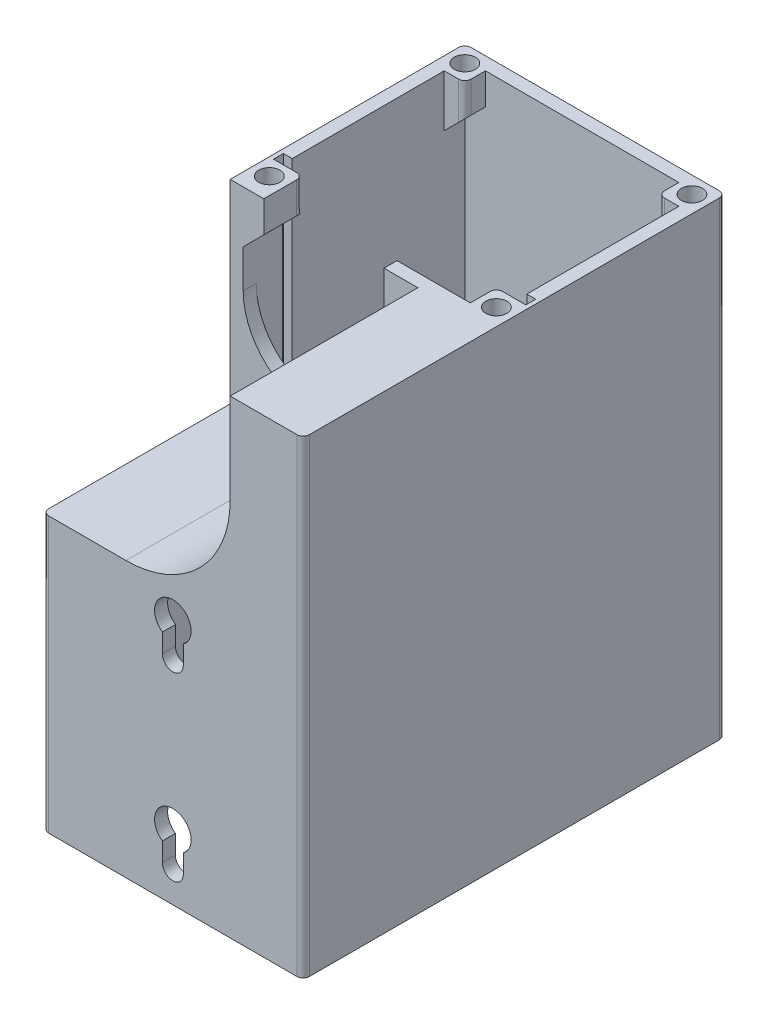
SolidWorks part; units mm, degrees
ref_plane "前基準面" through (0, 0, 0) normal (0, 0, 1) x (1, 0, 0)
ref_plane "上基準面" through (0, 0, 0) normal (0, 1, 0) x (1, 0, 0)
ref_plane "右基準面" through (0, 0, 0) normal (1, 0, 0) x (0, 0, -1)
sketch "草圖1" plane through (0, 0, 0) normal (0, 1, 0) x (1, 0, 0)
  line L1 (-25, -22.5) -> (25, -22.5)
  line L2 (-25, -22.5) -> (-25, 22.5)
  line L3 (-25, 22.5) -> (25, 22.5)
  line L4 (25, -22.5) -> (25, 22.5)
  line L5 (-25, -22.5) -> (25, 22.5) construction
  line L6 (-25, 22.5) -> (25, -22.5) construction
  line L7 (-22.5, -20) -> (22.5, -20)
  line L8 (-22.5, -20) -> (-22.5, 20)
  line L9 (-22.5, 20) -> (22.5, 20)
  line L10 (22.5, -20) -> (22.5, 20)
  line L11 (-22.5, -20) -> (22.5, 20) construction
  line L12 (-22.5, 20) -> (22.5, -20) construction
  point P0 (0, 0)
  point P6 (0, 0)
  point P11 (0, 0)
  point P12 (0, 0)
  dimension "D1" = 50
  dimension "D2" = 2.5
  dimension "D3" = 2.5
  dimension "D4" = 40
extrude "填料-伸長1" add sketch "草圖1" against normal blind 90
sketch "草圖2" plane through (0, 0, 0) normal (0, 1, 0) x (1, 0, 0)
  line L1 (24.2, -15) -> (-24.2, -15)
  line L2 (24.2, -15) -> (24.2, -13.1)
  line L3 (24.2, -13.1) -> (-24.2, -13.1)
  line L4 (-24.2, -15) -> (-24.2, -13.1)
  line L6 (-25, 22.5) -> (-25, -22.5) construction
  line L7 (25, -22.5) -> (25, 22.5) construction
  line L8 (-22.5, -20) -> (22.5, -20) construction
  dimension "D1" = 1.9
  dimension "D2" = 0.8
  dimension "D3" = 0.8
  dimension "D4" = 5
extrude "除料-伸長1" cut sketch "草圖2" against normal blind 36
sketch "草圖3" plane through (0, 0, 22.5) normal (0, 0, 1) x (1, 0, 0)
  line L0 (-25, -90) -> (-25, 0) construction
  line L1 (-25, 0) -> (25, 0) construction
  line L2 (-22.5, -17.3) -> (-22.5, 0)
  line L3 (-22.5, 0) -> (4.5, 0)
  line L4 (4.5, 0) -> (4.5, -17.3)
  circle A0 centre (-9, -17.3) radius 13.5
  line M3 (25, 0) -> (-25, 0)
  dimension "D3" = 27
  dimension "D1" = 16
  dimension "D2" = 17.3
extrude "除料-伸長2" cut sketch "草圖3" against normal up to surface (2.5 mm away) contours A0 L4 L2 M3 | A0 region at (-22.1793, -8.65, 22.5) region at (-9, -17.3, 22.5) up to face at (0, -45, 20)
sketch "草圖4" plane through (0, 0, 22.5) normal (0, 0, 1) x (1, 0, 0)
  line L0 (11, 0) -> (11, -17.3)
  line L1 (4.5, 0) -> (25, 0) construction
  line L2 (-9, -37.3) -> (-25, -37.3)
  line L3 (-25, -90) -> (-25, 0) construction
  line L4 (-25, -37.3) -> (-25, -90)
  line L5 (-25, -90) -> (25, -90)
  line L6 (25, -90) -> (25, 0)
  line L7 (25, 0) -> (11, 0)
  arc A0 (11, -17.3) -> (-9, -37.3) centre (-9, -17.3) cw
  arc A1 (-22.5, -17.3) -> (4.5, -17.3) centre (-9, -17.3) ccw construction
  arc A2 (-22.5, -17.3) -> (4.5, -17.3) centre (-9, -17.3) ccw construction
  circle A3 centre (-9, -17.3) radius 15 construction
  point P20 (-13.6326, -36.7561)
  point P21 (0, 0)
  point P22 (0, 0)
  point P23 (10.5076, -21.7106)
  dimension "D1" = 30
  dimension "D2" = 5
extrude "填料-伸長2" add sketch "草圖4" along normal blind 36
sketch "草圖5" plane through (-25, -90, 58.5) normal (0, -1, 0) x (1, 0, 0)
  line L0 (47.5, -38.5) -> (47.5, -78.5) construction
  line L1 (2.5, -38.5) -> (47.5, -38.5)
  line L2 (2.5, -38.5) -> (2.5, -2.5)
  line L3 (2.5, -2.5) -> (47.5, -2.5)
  line L4 (47.5, -38.5) -> (47.5, -2.5)
  line L7 (0, 0) -> (50, 0) construction
  dimension "D1" = 2.5
extrude "除料-伸長3" cut sketch "草圖5" against normal offset from surface (50.2 mm away) 2.5 up to face at (-17, -37.3, 40.5)
sketch "草圖6" plane through (0, 0, 20) normal (0, 0, -1) x (-1, 0, 0)
  line L0 (-22.5, -2.5) -> (-22.5, -39.8)
  line L1 (-22.5, -39.8) -> (22.5, -39.8) construction
  line L2 (-22.5, -39.8) -> (9, -39.8)
  line L3 (-22.5, -2.5) -> (-13.5, -2.5)
  line L4 (-13.5, -2.5) -> (-13.5, -17.3)
  line L5 (-25, 0) -> (25, 0) construction
  line L7 (-22.5, -90) -> (-22.5, 0) construction
  arc A0 (-13.5, -17.3) -> (9, -39.8) centre (9, -17.3) ccw
  arc A1 (-11, -17.3) -> (9, -37.3) centre (9, -17.3) ccw construction
  dimension "D1" = 2.5
  dimension "D2" = 2.5
extrude "除料-伸長4" cut sketch "草圖6" against normal up to surface (36 mm away) up to face at (0, -64.9, 56)
ref_plane "平面2" through (0, -38.5, 0) normal (0, 1, 0) x (1, 0, 0)
sketch "草圖7" plane through (0, -38.5, 0) normal (0, 1, 0) x (1, 0, 0)
  line L1 (-20.3, -13.1) -> (-22.5, -13.1)
  line L2 (-20.3, -13.1) -> (-20.3, -15)
  line L3 (-20.3, -15) -> (-22.5, -15)
  line L4 (-22.5, -13.1) -> (-22.5, -15)
  line L5 (24.2, -13.1) -> (22.5, -13.1) construction
  line L6 (22.5, -15) -> (24.2, -15) construction
  line L7 (-22.5, 20) -> (-22.5, -56) construction
  dimension "D1" = 2.2
extrude "填料-伸長3" add sketch "草圖7" against normal blind 30
chamfer "導角1" distance 2.2 angle 45 2 edges at (-20.3, -38.5, 14.05) (-20.3, -68.5, 14.05)
sketch "草圖8" plane through (0, -90, 0) normal (0, -1, 0) x (1, 0, 0)
  line L0 (-25, 58.5) -> (25, 58.5) construction
  line L1 (-25, -22.5) -> (-25, 58.5) construction
  line L2 (25, -22.5) -> (-25, -22.5) construction
  line L3 (-22.5, 56) -> (-18.55, 56)
  line L4 (-22.5, 56) -> (-22.5, 52.05)
  line L5 (-22.5, 52.05) -> (-18.55, 52.05)
  line L6 (-18.55, 56) -> (-18.55, 52.05)
  line L7 (22.5, 56) -> (18.55, 56)
  line L8 (22.5, 56) -> (22.5, 52.05)
  line L9 (22.5, 52.05) -> (18.55, 52.05)
  line L10 (18.55, 56) -> (18.55, 52.05)
  line L11 (22.5, -20) -> (18.55, -20)
  line L12 (22.5, -20) -> (22.5, -16.05)
  line L13 (22.5, -16.05) -> (18.55, -16.05)
  line L14 (18.55, -20) -> (18.55, -16.05)
  line L15 (-22.5, -20) -> (-18.55, -20)
  line L16 (-22.5, -20) -> (-22.5, -16.05)
  line L17 (-22.5, -16.05) -> (-18.55, -16.05)
  line L18 (-18.55, -20) -> (-18.55, -16.05)
  line L19 (25, 58.5) -> (25, -22.5) construction
  circle A0 centre (-21.775, 55.275) radius 2.025 construction
  circle A1 centre (21.775, -19.275) radius 2.025 construction
  point P28 (16.712, -10.6602)
  dimension "D1" = 4.05
  dimension "D2" = 3.225
  dimension "D3" = 3.225
  dimension "D4" = 3.225
  dimension "D5" = 3.225
  dimension "D6" = 3.225
  dimension "D7" = 3.225
  dimension "D8" = 3.225
  dimension "D9" = 3.225
extrude "填料-伸長4" add sketch "草圖8" against normal blind 6
sketch "草圖9" plane through (0, -90, 0) normal (0, -1, 0) x (1, 0, 0)
  line L0 (-25, 58.5) -> (25, 58.5) construction
  line L1 (-25, -22.5) -> (-25, 58.5) construction
  line L4 (25, 58.5) -> (25, -22.5) construction
  line L5 (25, -22.5) -> (-25, -22.5) construction
  circle A0 centre (-21.775, 55.275) radius 2.025
  circle A1 centre (21.775, 55.275) radius 2.025
  circle A2 centre (-21.775, -19.275) radius 2.025
  circle A3 centre (21.775, -19.275) radius 2.025
  point P12 (22.5, 56)
  point P15 (22.5, -18.9206)
  point P16 (-22.5, -18.9206)
  point P17 (0, 0)
  point P18 (0, 0)
  point P19 (0, 0)
  point P20 (0, 0)
  point P21 (0, 0)
  point P22 (22.5, -18.7775)
  point P23 (22.5, 55.275)
  point P24 (0, 0)
  dimension "D1" = 4.05
  dimension "D2" = 3.225
  dimension "D3" = 3.225
  dimension "D4" = 3.225
  dimension "D5" = 3.225
extrude "除料-伸長5" cut sketch "草圖9" against normal blind 5
sketch "草圖10" plane through (0, 0, 0) normal (0, 1, 0) x (1, 0, 0)
  line L0 (25, -58.5) -> (25, 22.5) construction
  line L1 (-9, -22.5) -> (11, -22.5) construction
  line L2 (-25, -22.5) -> (-22.5, -22.5) construction
  line L3 (22.5, -20) -> (18.55, -20)
  line L4 (22.5, -20) -> (22.5, -15)
  line L5 (22.5, -15) -> (18.55, -15)
  line L6 (18.55, -20) -> (18.55, -15)
  line L7 (-22.5, -22.5) -> (-18.55, -22.5)
  line L8 (-22.5, -22.5) -> (-22.5, -15)
  line L9 (-22.5, -15) -> (-18.55, -15)
  line L10 (-18.55, -22.5) -> (-18.55, -15)
  line L11 (-22.5, 20) -> (-18.55, 20)
  line L12 (-22.5, 20) -> (-22.5, 16.05)
  line L13 (-22.5, 16.05) -> (-18.55, 16.05)
  line L14 (-18.55, 20) -> (-18.55, 16.05)
  line L15 (22.5, 20) -> (18.55, 20)
  line L16 (22.5, 20) -> (22.5, 16.05)
  line L17 (22.5, 16.05) -> (18.55, 16.05)
  line L18 (18.55, 20) -> (18.55, 16.05)
  line L19 (-22.5, -15) -> (-22.5, -22.5) construction
  line L21 (22.5, -15) -> (24.2, -15) construction
  circle A0 centre (21.775, -19.275) radius 2.025 construction
  point P28 (-22.4834, -25.5668)
  dimension "D1" = 4.05
  dimension "D2" = 3.225
  dimension "D3" = 3.225
  dimension "D4" = 3.225
extrude "填料-伸長5" add sketch "草圖10" against normal blind 6
sketch "草圖11" plane through (0, 0, 0) normal (0, 1, 0) x (1, 0, 0)
  line L0 (24.2, -15) -> (18.55, -15) construction
  line L1 (18.55, -15) -> (18.55, -20) construction
  line L2 (25, 22.5) -> (-25, 22.5) construction
  line L3 (-25, 22.5) -> (-25, -22.5) construction
  circle A0 centre (21.775, -18.225) radius 2.025
  circle A1 centre (-21.775, -18.225) radius 2.025
  circle A2 centre (21.775, 19.275) radius 2.025
  circle A3 centre (-21.775, 19.275) radius 2.025
  point P8 (61.5727, -44.4893)
  point P9 (21.5396, -18.9247)
  point P14 (-22.0107, -18.1792)
  point P15 (0, 0)
  point P16 (-20.8284, 18.025)
  point P17 (0, 0)
  point P18 (0, 0)
  dimension "D1" = 4.05
  dimension "D2" = 3.225
  dimension "D3" = 3.225
  dimension "D4" = 3.225
  dimension "D5" = 3.225
extrude "除料-伸長6" cut sketch "草圖11" against normal blind 5
chamfer "導角2" distance 3.95 angle 45 4 edges at (-22.5, -6, 18.75) (22.5, -6, 17.5) (22.5, -6, -18.025) (-22.5, -6, -18.025)
fillet "圓角1" radius 1.2 12 edges at (18.55, -87, 52.05) (-18.55, -87, 52.05) (18.55, -87, -16.05) (-18.55, -87, -16.05) (-18.55, -3, 15) (-18.55, -3, -16.05) (18.55, -3, -16.05) (18.55, -3, 15) (25, -45, 58.5) (-25, -63.65, 58.5) (-25, -45, -22.5) (25, -45, -22.5)
sketch "草圖12" plane through (0, 0, 58.5) normal (0, 0, 1) x (1, 0, 0)
  line L0 (-2, -49.3) -> (-2, -45.6723)
  line L1 (2, -49.3) -> (2, -45.6723)
  line L2 (-9, -37.3) -> (-23.8, -37.3) construction
  line L3 (-2, -84) -> (-2, -80.3723)
  line L4 (2, -84) -> (2, -80.3723)
  line L5 (-23.8, -90) -> (23.8, -90) construction
  circle A0 centre (0, -42.8) radius 3.5 construction
  circle A1 centre (0, -49.3) radius 2 construction
  arc A2 (-2, -49.3) -> (2, -49.3) centre (0, -49.3) ccw
  arc A3 (-2, -45.6723) -> (2, -45.6723) centre (0, -42.8) cw
  circle A4 centre (0, -77.5) radius 3.5 construction
  circle A5 centre (0, -84) radius 2 construction
  arc A6 (-2, -84) -> (2, -84) centre (0, -84) ccw
  arc A7 (-2, -80.3723) -> (2, -80.3723) centre (0, -77.5) cw
  point P23 (0, 0)
  dimension "D1" = 7
  dimension "D2" = 4
  dimension "D5" = 7
  dimension "D6" = 4
  dimension "D3" = 6.5
  dimension "D4" = 5.5
  dimension "D7" = 6.5
  dimension "D8" = 6
extrude "除料-伸長7" cut sketch "草圖12" against normal up to next
